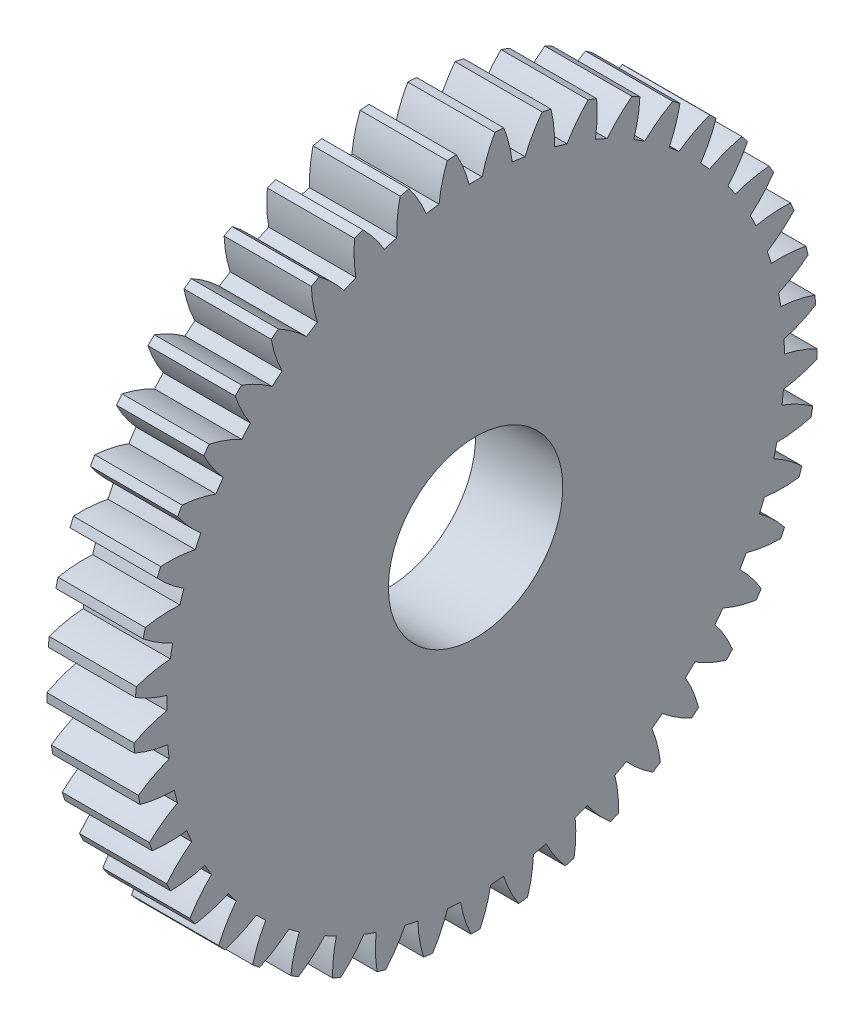
SolidWorks part; units mm, degrees
ref_plane "Plane1" through (0, 0, 0) normal (0, 0, 1) x (1, 0, 0)
ref_plane "Plane2" through (0, 0, 0) normal (0, 1, 0) x (1, 0, 0)
ref_plane "Plane3" through (0, 0, 0) normal (1, 0, 0) x (0, 0, -1)
other "Configuration Table"
sketch "HoldingSke" plane through (0, 0, 0) normal (0, 1, 0) x (1, 0, 0)
  line L0 (0, 0) -> (431.0523, -431.0523)
  line L1 (-15, 0) -> (100, 0) construction
  line L2 (0, 0) -> (-2.1039, 2.3779)
  line L3 (0, 0) -> (-11.863, 4.5341)
  line L4 (0, 0) -> (6.1066, 6.1066)
  line L5 (0, 0) -> (-47.5972, -17.7524)
  line L6 (0, 0) -> (-5.2639, -3.5516)
  line L7 (-2.1039, 2.3779) -> (8.8308, 51.9871)
  line L8 (-76.2, 54.61) -> (-75.184, 54.61)
  line L9 (-71.009, 38.7566) -> (-53.1078, 45.2721)
  line L10 (-76.2, 71.12) -> (104.1128, 71.12)
  line L11 (0, 0) -> (-6.35, 0)
  line L12 (-76.2, 101.6) -> (-76.1573, 101.6)
  line L13 (24.9733, 27.94) -> (52.9518, 28.4284)
  line L14 (24.9733, 27.94) -> (25.0241, 27.9398)
  line L15 (24.9733, 27.94) -> (100.4021, 29.52)
  circle A0 centre (0, 0) radius 0.3969
  circle A1 centre (0, 0) radius 22.4917
  circle A2 centre (0, 0) radius 38.1
  circle A3 centre (0, 0) radius 0.3969
  dimension "Num_teeth" = 45
  dimension "H" = 19.05
  dimension "Pitch_radius" = 180.3128
  dimension "Width" = 6.35
  dimension "Thickness" = 6.35
sketch "BasProSke" plane through (0, 0, 0) normal (0, 1, 0) x (1, 0, 0)
  line L0 (-10, 0) -> (60, 0) construction
  line L1 (0, 0) -> (0, 24.8708)
  line L2 (0, 0) -> (6.35, 0)
  line L3 (6.35, 0) -> (6.35, 24.8708)
  line L4 (6.35, 24.8708) -> (0, 24.8708)
  dimension "Thickness" = 6.35
  dimension "Diameter" = 49.7417
revolve "Base-Revolve" add sketch "BasProSke" angle 360 about L0
sketch "TooCutSke" plane through (0, 0, 0) normal (1, 0, 0) x (0, 0, -1)
  line L1 (0, 0) -> (0, 107) construction
  line L2 (0, 0) -> (-0.9057, 23.7953) construction
  line L3 (0, 0) -> (-3.3205, 47.485) construction
  line L4 (-0.9057, 23.7953) -> (-1.6602, 23.7425) construction
  arc A0 (0.4733, 22.4867) -> (-0.4733, 22.4867) centre (0, 0) ccw
  arc A1 (1.4225, 24.8556) -> (-1.4225, 24.8556) centre (0, 0) ccw
  circle A2 centre (0, 0) radius 23.8125 construction
  circle A3 centre (0, 0) radius 22.3764 construction
  arc A4 (-0.4733, 22.4867) -> (-1.4225, 24.8556) centre (-9.7097, 20.16) ccw
  arc A5 (1.4225, 24.8556) -> (0.4733, 22.4867) centre (9.7097, 20.16) ccw
extrude "ToothCut" cut sketch "TooCutSke" along normal through all
fillet "Breaks" [suppressed] radius 0.0212 tangent propagation no
fillet "RootFillets" [suppressed] radius 0.2625
pattern_circular "TeethCuts" count 45 every 8 about axis through (-10, 0, 0) along (1, 0, 0) of "ToothCut", "RootFillets", "Breaks"
sketch "HubNeaOneSke" plane through (0, 0, 0) normal (-1, 0, 0) x (0, 0, 1)
  circle A0 centre (0, 0) radius 22.4917
  dimension "Diameter" = 44.9834
extrude "HubNearOne" [suppressed] add sketch "HubNeaOneSke" along normal blind 44.4501
sketch "HubNeaBotSke" plane through (0, 0, 0) normal (-1, 0, 0) x (0, 0, 1)
  circle A0 centre (0, 0) radius 22.4917
  dimension "Diameter" = 44.9834
extrude "HubNearBoth" [suppressed] add sketch "HubNeaBotSke" along normal blind 22.225
ref_plane "FarPln" through (6.35, 0, 0) normal (1, 0, 0) x (0, 0, -1)
sketch "HubFarSke" plane through (6.35, 0, 0) normal (1, 0, 0) x (0, 0, -1)
  circle A0 centre (0, 0) radius 22.4917
  dimension "Diameter" = 44.9834
extrude "HubFar" [suppressed] add sketch "HubFarSke" along normal blind 22.225
sketch "BorSke" plane through (0, 0, 0) normal (1, 0, 0) x (0, 0, -1)
  circle A0 centre (0, 0) radius 0.3969
  dimension "Diameter" = 0.7937
extrude "Bore" cut sketch "BorSke" along normal mid plane 101.6001
sketch "KeySke" plane through (0, 0, 0) normal (1, 0, 0) x (0, 0, -1)
  line L0 (-0.127, 0) -> (-0.127, 0.6191)
  line L1 (-0.127, 0.6191) -> (0.127, 0.6191)
  line L2 (0.127, 0.6191) -> (0.127, 0)
  line L3 (0, 0) -> (0, 34) construction
  line L4 (-0.127, 0) -> (0.127, 0)
  dimension "Width" = 0.254
extrude "Keyway" [suppressed] cut sketch "KeySke" along normal mid plane 101.6001
pattern_circular "Keyway2" [suppressed] count 2 every 90 about axis through (-10, 0, 0) along (1, 0, 0)
sketch "Sketch1" plane through (0, 0, 0) normal (-1, 0, 0) x (0, 0, 1)
  circle A0 centre (0, 0) radius 6.35
  dimension "D1" = 12.7
extrude "Cut-Extrude1" cut sketch "Sketch1" against normal through all
equation "' \"Pitch@HoldingSke\" = 4"
equation "' \"Num_teeth@HoldingSke\" = 12"
equation "' \"Ap@HoldingSke\" =  20"
equation "' \"Ap@HoldingSke\" = 20"
equation "' \"Width@HoldingSke\" = 0.5"
equation "' \"Hub_dia@HoldingSke\"= 1"
equation "' \"Hub_dia@HoldingSke\" = 1"
equation "' \"Overall_len@HoldingSke\" = 1.0"
equation "' \"Bore@HoldingSke\" = 0.75"
equation "' \"T_dim@HoldingSke\" = 0.85"
equation "' \"Width@KeySke\" = 0.25"
equation "' \"Show_teeth@HoldingSke\" = 13"
equation "' \"Backlash@HoldingSke\" = 0.009"
equation "' \"Addendum_fac@HoldingSke\" = 1.0"
equation "' \"Dedendum_fac@HoldingSke\" = 1.25"
equation "' \"Dedendum_add@HoldingSke\" = 0.00005"
equation "' \"Clearance_fac@HoldingSke\" = 0.25"
equation "' \"Pitch@HoldingSke\" = 0.5"
equation "' \"Num_teeth@HoldingSke\" = 23"
equation "' \"Show_teeth@HoldingSke\" = 23"
equation "' \"Backlash@HoldingSke\" = 0.0375"
equation "\"Overcut_dia@TooCutSke\" = (\"Num_teeth@HoldingSke\" + 2 * \"Addendum_fac@HoldingSke\") / \"Pitch@HoldingSke\" + 0.002"
equation "\"Pitch_dia@TooCutSke\" = \"Num_teeth@HoldingSke\" / \"Pitch@HoldingSke\""
equation "\"Base_dia@TooCutSke\" = \"Num_teeth@HoldingSke\" / \"Pitch@HoldingSke\" * cos((\"Ap@HoldingSke\"  * 3.14159265 / 180))"
equation "\"Root_dia@TooCutSke\" = (\"Num_teeth@HoldingSke\" + 2) / \"Pitch@HoldingSke\" - 2 * (\"Addendum_fac@HoldingSke\" + \"Dedendum_fac@HoldingSke\") / \"Pitch@HoldingSke\" - \"Dedendum_add@HoldingSke\" * 2"
equation "\"Half_ang@TooCutSke\" = 180 / \"Num_teeth@HoldingSke\""
equation "\"Half_CT@TooCutSke\" = \"Num_teeth@HoldingSke\" / \"Pitch@HoldingSke\" * sin((3.14159265 / 2 / \"Num_teeth@HoldingSke\")) / 2 - 7 * \"Backlash@HoldingSke\" / 4"
equation "\"Flank_rad@TooCutSke\" = \"Num_teeth@HoldingSke\" / \"Pitch@HoldingSke\" / 5"
equation "\"Radius@RootFillets\" = \"Clearance_fac@HoldingSke\" / \"Pitch@HoldingSke\" + \"Dedendum_add@HoldingSke\""
equation "\"Break_rad@Breaks\" = 0.02 / \"Pitch@HoldingSke\""
equation "\"Thickness@HoldingSke\" = \"Width@HoldingSke\""
equation "\"OAL@HoldingSke\" = \"Thickness@HoldingSke\""
equation "\"MHD@HoldingSke\" = (\"Num_teeth@HoldingSke\" + 2) / \"Pitch@HoldingSke\" - 2 * (\"Addendum_fac@HoldingSke\" + \"Dedendum_fac@HoldingSke\")  / \"Pitch@HoldingSke\" - \"Dedendum_add@HoldingSke\" * 2"
equation "\"MBD@HoldingSke\" = (\"Num_teeth@HoldingSke\" + 2) / \"Pitch@HoldingSke\" - 2 * (\"Addendum_fac@HoldingSke\" + \"Dedendum_fac@HoldingSke\")  / \"Pitch@HoldingSke\" - \"Dedendum_add@HoldingSke\" * 2 - 0.002"
equation "\"MHD@HoldingSke\" = ((sgn( \"MHD@HoldingSke\" - \"Hub_dia@HoldingSke\" )-1)*( \"MHD@HoldingSke\" - \"Hub_dia@HoldingSke\" ))/-2+ \"Hub_dia@HoldingSke\""
equation "\"MBD@HoldingSke\" = ((sgn( \"MBD@HoldingSke\" - \"Bore@HoldingSke\" )-1)*( \"MBD@HoldingSke\" - \"Bore@HoldingSke\" ))/-2+ \"Bore@HoldingSke\""
equation "\"OAL@HoldingSke\" = ((sgn( \"OAL@HoldingSke\" - \"Overall_len@HoldingSke\" )+1)*( \"OAL@HoldingSke\" - \"Overall_len@HoldingSke\" ))/2 + \"Overall_len@HoldingSke\" + 0.000002"
equation "\"Num_teeth@TeethCuts\" = int( \"Show_teeth@HoldingSke\" ) + 1"
equation "\"Num_teeth@TeethCuts\" = ((sgn( \"Num_teeth@TeethCuts\" - \"Num_teeth@HoldingSke\" )-1)*( \"Num_teeth@TeethCuts\" - \"Num_teeth@HoldingSke\" ))/-2+ \"Num_teeth@HoldingSke\""
equation "\"Num_teeth@TeethCuts\" = ((sgn( \"Num_teeth@TeethCuts\" - 2.0)+1)*( \"Num_teeth@TeethCuts\" - 2.0))/2 +2.0"
equation "\"Angle@TeethCuts\" = 360.0 / \"Num_teeth@HoldingSke\""
equation "\"Diameter@BasProSke\" = (\"Num_teeth@HoldingSke\" + 2 * \"Addendum_fac@HoldingSke\") / \"Pitch@HoldingSke\""
equation "\"Thickness@BasProSke\"  = \"Thickness@HoldingSke\""
equation "' \"Fillet_rad@BasProSke\" =  \"Thickness@HoldingSke\" * 0.05"
equation "' \"Fillet_rad@BasProSke\" = \"Thickness@HoldingSke\" * 0.05"
equation "\"MHD@HoldingSke\" = ((sgn( \"MHD@HoldingSke\" - \"Root_dia@TooCutSke\" )-1)*( \"MHD@HoldingSke\" - \"Root_dia@TooCutSke\" ))/-2+ \"Root_dia@TooCutSke\""
equation "\"Diameter@HubNeaOneSke\" = \"MHD@HoldingSke\""
equation "\"Length@HubNearOne\" = \"OAL@HoldingSke\" - \"Thickness@BasProSke\""
equation "\"Diameter@HubNeaBotSke\" = \"MHD@HoldingSke\""
equation "\"Length@HubNearBoth\" = ( \"OAL@HoldingSke\" - \"Thickness@BasProSke\" ) / 2.0"
equation "\"Thickness@FarPln\" = \"Thickness@BasProSke\""
equation "\"Diameter@HubFarSke\" = \"MHD@HoldingSke\""
equation "\"Length@HubFar\" = ( \"OAL@HoldingSke\" - \"Thickness@BasProSke\" ) / 2.0"
equation "\"Diameter@BorSke\" = \"MBD@HoldingSke\""
equation "\"D1@Bore\" = \"OAL@HoldingSke\" * 2.0"
equation "\"D1@Keyway\" = \"OAL@HoldingSke\" * 2.0"
equation "\"Offset@KeySke\" = \"T_dim@HoldingSke\" - \"MBD@HoldingSke\" / 2.0"
